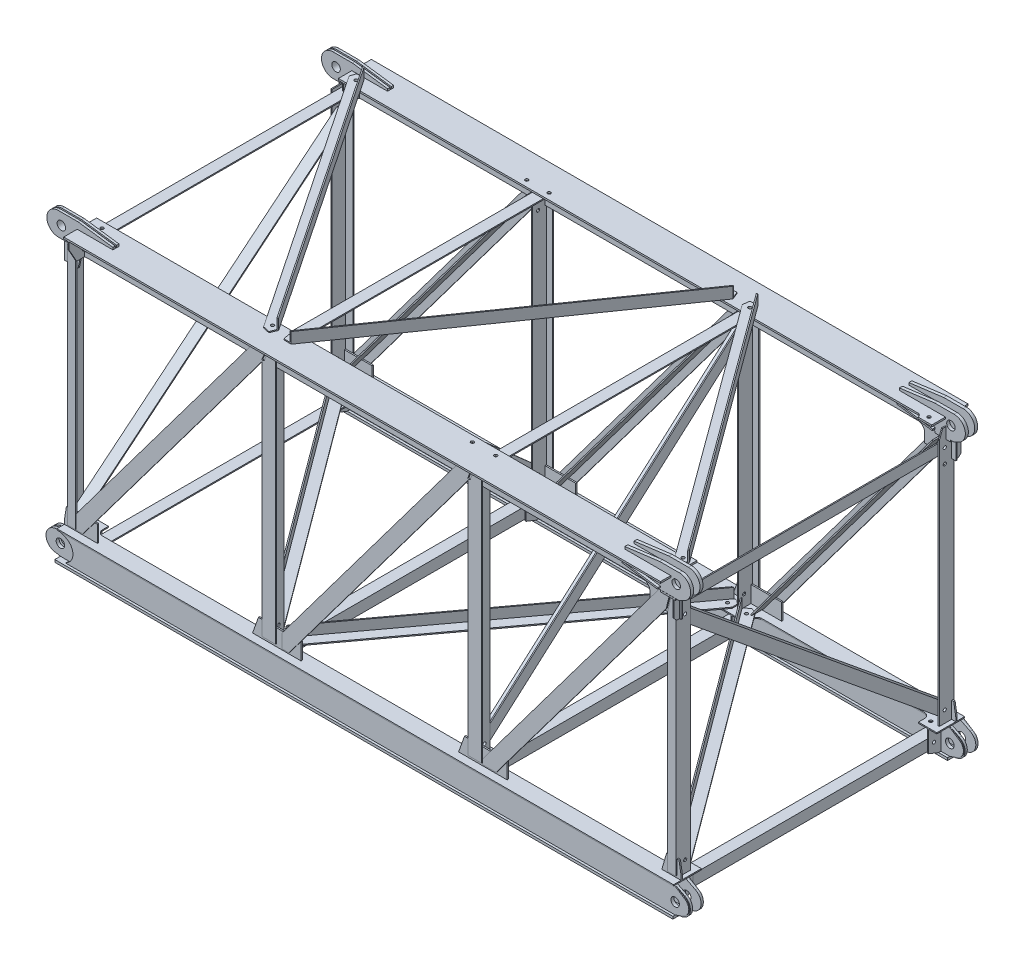
SolidWorks part; units mm, degrees
ref_plane "前视基准面" through (0, 0, 0) normal (0, 0, 1) x (1, 0, 0)
ref_plane "上视基准面" through (0, 0, 0) normal (0, 1, 0) x (1, 0, 0)
ref_plane "右视基准面" through (0, 0, 0) normal (1, 0, 0) x (0, 0, -1)
sketch "草图2" plane through (0, 0, 0) normal (0, 0, 1) x (1, 0, 0)
  line L0 (-1000, 2000) -> (49000, 2000) construction
  line L1 (-22, 1926) -> (5, 1926)
  line L2 (5, 1926) -> (5, 1776)
  line L3 (-22, 2074) -> (119, 2074)
  line L4 (5, 1776) -> (105, 1776)
  line L5 (117.1113, 1832.4829) -> (105, 1776)
  line L6 (166, 1872) -> (4218, 1872)
  line L7 (119, 2074) -> (375, 2040)
  line L8 (375, 2040) -> (375, 2022)
  line L9 (375, 2022) -> (4385, 2022)
  line L10 (4385, 2022) -> (4385, 1895)
  line L11 (4385, 1895) -> (4495, 1895)
  line L12 (4495, 1895) -> (4495, 1755)
  line L13 (4495, 1755) -> (4268, 1755)
  line L14 (4268, 1755) -> (4268, 1822)
  circle A0 centre (0, 2000) radius 31
  arc A1 (-22, 2074) -> (-22, 1926) centre (-22, 2000) ccw
  arc A2 (117.1113, 1832.4829) -> (166, 1872) centre (166, 1822) cw
  arc A3 (4268, 1822) -> (4218, 1872) centre (4218, 1822) ccw
  dimension "D1" = 62
  dimension "D4" = 74
  dimension "D10" = 50
  dimension "D19" = 50
  dimension "D2" = 2000
  dimension "D3" = 22
  dimension "D5" = 27
  dimension "D6" = 150
  dimension "D7" = 141
  dimension "D8" = 100
  dimension "D9" = 61
  dimension "D11" = 256
  dimension "D12" = 34
  dimension "D13" = 18
  dimension "D14" = 4010
  dimension "D15" = 127
  dimension "D16" = 110
  dimension "D17" = 140
  dimension "D18" = 227
  dimension "D20" = 117
extrude "凸台-拉伸1" add sketch "草图2" along normal blind 10
sketch "草图3" plane through (0, 2022, 0) normal (0, 1, 0) x (1, 0, 0)
  line L0 (-625, -5) -> (49375, -5) construction
  line L1 (375, -10) -> (375, 0) construction
  line L2 (115, 115) -> (115, 17)
  line L3 (115, 17) -> (375, 17)
  line L4 (375, 17) -> (375, -27)
  line L5 (375, -27) -> (115, -27)
  line L6 (115, -27) -> (115, -125)
  line L7 (115, -125) -> (4460, -125)
  line L8 (4460, -125) -> (4460, -50)
  line L9 (4460, -50) -> (4125, -50)
  line L10 (4125, -50) -> (4125, -28)
  line L11 (4125, -28) -> (4385, -28)
  line L12 (4385, -28) -> (4385, 18)
  line L13 (4385, 18) -> (4125, 18)
  line L14 (4125, 18) -> (4125, 40)
  line L15 (4125, 40) -> (4460, 40)
  line L16 (4460, 40) -> (4460, 140)
  line L17 (4335, 115) -> (115, 115)
  line L18 (4360, 140) -> (4460, 140)
  line L19 (4385, -10) -> (4385, 0) construction
  line L20 (-580.0707, 70) -> (49419.9293, 70) construction
  arc A0 (4335, 115) -> (4360, 140) centre (4335, 140) ccw
  circle A1 centre (199, 70) radius 11.5
  circle A2 centre (1440.6, 70) radius 11.5
  circle A3 centre (1604, 70) radius 11.5
  circle A4 centre (2896, 70) radius 11.5
  circle A5 centre (3066, 70) radius 11.5
  circle A6 centre (4400, 100) radius 11.5
  point P5 (375, -5)
  dimension "D8" = 25
  dimension "D12" = 23
  dimension "D18" = 23
  dimension "D1" = 44
  dimension "D2" = 98
  dimension "D3" = 260
  dimension "D4" = 4345
  dimension "D5" = 75
  dimension "D6" = 335
  dimension "D7" = 22
  dimension "D9" = 45
  dimension "D10" = 100
  dimension "D11" = 100
  dimension "D13" = 84
  dimension "D14" = 1241.6
  dimension "D15" = 163.4
  dimension "D16" = 170
  dimension "D17" = 1292
  dimension "D19" = 40
  dimension "D20" = 60
extrude "凸台-拉伸2" add sketch "草图3" along normal blind 12
sketch "草图4" plane through (0, 0, 0) normal (1, 0, 0) x (0, 0, -1)
  line L0 (-5, -1000) -> (-5, 49000) construction
  line L1 (-75, -82) -> (65, -82)
  line L2 (-75, -82) -> (-75, -100)
  line L3 (-75, -100) -> (-25, -100)
  line L4 (65, -82) -> (65, -100)
  line L5 (-5, 776) -> (-5, 50776) construction
  line L6 (-10, 1776) -> (0, 1776) construction
  line L7 (-25, -100) -> (-25, -90)
  line L8 (-25, -90) -> (15, -90)
  line L9 (15, -90) -> (15, -100)
  line L10 (15, -100) -> (65, -100)
  point P12 (-5, 1776)
  dimension "D1" = 140
  dimension "D2" = 18
  dimension "D3" = 82
  dimension "D4" = 10
  dimension "D5" = 50
  dimension "D6" = 50
extrude "凸台-拉伸3" add sketch "草图4" along normal blind 4500 separate body
sketch "草图5" plane through (0, 0, 0) normal (-1, 0, 0) x (0, 0, 1)
  line L0 (-65, -82) -> (75, -82) construction
  line L1 (-138, 110) -> (65, 110)
  line L2 (-138, 110) -> (-138, 102)
  line L3 (-138, 102) -> (65, 102)
  line L4 (65, 110) -> (65, 102)
  line L6 (5, 776) -> (5, 50776) construction
  line L7 (10, 1776) -> (0, 1776) construction
  point P14 (5, 1776)
  dimension "D1" = 184
  dimension "D2" = 60
  dimension "D3" = 203
  dimension "D4" = 8
extrude "凸台-拉伸4" add sketch "草图5" against normal blind 4495 separate body
sketch "草图6" plane through (0, 110, 0) normal (0, 1, 0) x (1, 0, 0)
  line L0 (4495, 138) -> (0, 138) construction
  line L1 (0, -65) -> (5, -65)
  line L2 (0, -65) -> (0, 138)
  line L3 (0, 138) -> (5, 138)
  line L4 (5, -65) -> (5, 138)
  line L5 (-62.0631, 88) -> (49937.9369, 88) construction
  line L6 (218, 55) -> (1360, 55)
  line L7 (4495, -65) -> (0, -65) construction
  line L8 (178, 138) -> (178, 95)
  line L9 (218, 95) -> (50218, 95) construction
  line L10 (1400, 95) -> (1400, 138)
  line L11 (1620, 138) -> (2880, 138)
  line L12 (1620, 138) -> (1620, 95)
  line L13 (1660, 55) -> (2840, 55)
  line L14 (2880, 95) -> (2880, 138)
  line L15 (3100, 138) -> (4361, 138)
  line L16 (3100, 138) -> (3100, 95)
  line L17 (3140, 55) -> (4321, 55)
  line L18 (4361, 95) -> (4361, 138)
  line L19 (178, 138) -> (1400, 138)
  circle A0 centre (98, 88) radius 11.5
  arc A1 (178, 95) -> (218, 55) centre (218, 95) ccw
  arc A2 (1360, 55) -> (1400, 95) centre (1360, 95) ccw
  circle A3 centre (1440, 88) radius 11.5
  circle A4 centre (1579, 88) radius 11.5
  arc A5 (1620, 95) -> (1660, 55) centre (1660, 95) ccw
  arc A6 (2840, 55) -> (2880, 95) centre (2840, 95) ccw
  arc A7 (3100, 95) -> (3140, 55) centre (3140, 95) ccw
  circle A8 centre (2921, 88) radius 11.5
  circle A9 centre (3059, 88) radius 11.5
  arc A10 (4321, 55) -> (4361, 95) centre (4321, 95) ccw
  circle A11 centre (4401, 88) radius 11.5
  dimension "D3" = 23
  dimension "D5" = 40
  dimension "D7" = 213
  dimension "D9" = 40
  dimension "D12" = 40
  dimension "D14" = 40
  dimension "D18" = 40
  dimension "D20" = 40
  dimension "D1" = 5
  dimension "D2" = 50
  dimension "D4" = 93
  dimension "D6" = 120
  dimension "D8" = 1142
  dimension "D10" = 1342
  dimension "D11" = 139
  dimension "D13" = 300
  dimension "D15" = 1180
  dimension "D16" = 1342
  dimension "D17" = 138
  dimension "D19" = 300
  dimension "D21" = 1181
  dimension "D22" = 1342
extrude "切除-拉伸1" cut sketch "草图6" against normal blind 8
sketch "草图7" plane through (0, 0, 0) normal (-1, 0, 0) x (0, 0, 1)
  line L0 (5, 926) -> (5, 50926) construction
  line L1 (10, 1926) -> (0, 1926) construction
  line L2 (65, 102) -> (-138, 102) construction
  line L3 (-48, 102) -> (-42, 102)
  line L4 (-48, 102) -> (-48, -82)
  line L5 (-48, -82) -> (-42, -82)
  line L6 (-42, 102) -> (-42, -82)
  line L7 (-65, -82) -> (75, -82) construction
  line L8 (75, -82) -> (75, -100) construction
  line L9 (52, 102) -> (58, 102)
  line L10 (52, 102) -> (52, -82)
  line L11 (52, -82) -> (58, -82)
  line L12 (58, 102) -> (58, -82)
  point P5 (5, 1926)
  point P17 (75, -91)
  dimension "D1" = 17
  dimension "D2" = 6
extrude "凸台-拉伸5" add sketch "草图7" against normal blind 4600
sketch "草图9" plane through (0, 0, 58) normal (0, 0, 1) x (1, 0, 0)
  line L0 (3424.3728, 0) -> (53424.3728, 0) construction
  line L1 (4500, -82) -> (0, -82) construction
  line L3 (4556.6629, -60.9212) -> (4500, -82)
  line L4 (4568.969, 54.7921) -> (4495, 102)
  line L5 (4600, 102) -> (4495, 102) construction
  line L6 (0, 102) -> (12, 102)
  line L7 (4495, 102) -> (5, 102) construction
  line L8 (12, 102) -> (12, 97)
  line L9 (0, 102) -> (0, -82)
  line L10 (0, -82) -> (66, -82)
  line L11 (4500, -82) -> (0, -82) construction
  line L12 (66, -82) -> (66, -77)
  line L13 (4495, 102) -> (4495, 110) construction
  line L14 (12, 97) -> (59.0619, 79.8775)
  line L15 (4500, 1374.2832) -> (4500, 51374.2832) construction
  line L16 (4495, 102) -> (4600, 102)
  line L17 (4600, 102) -> (4600, -82)
  line L18 (4600, -82) -> (4500, -82)
  circle A0 centre (4500, 0) radius 31
  arc A1 (4568.969, 54.7921) -> (4556.6629, -60.9212) centre (4534, 0) cw
  arc A2 (59.0619, 79.8775) -> (66, -77) centre (30, 0) cw
  circle A3 centre (0, 2000) radius 31 construction
  dimension "D2" = 62
  dimension "D3" = 65
  dimension "D5" = 85
  dimension "D6" = 4500
  dimension "D1" = 82
  dimension "D4" = 34
  dimension "D7" = 36
  dimension "D8" = 54
  dimension "D9" = 5
  dimension "D10" = 4434
extrude "切除-拉伸2" cut sketch "草图9" against normal through all
sketch "草图10" plane through (5, 0, 0) normal (-1, 0, 0) x (0, 0, 1)
  line L0 (5, -1090) -> (5, 48910) construction
  line L1 (25, -90) -> (-15, -90) construction
  line L2 (65, 110) -> (-138, 110) construction
  line L3 (0, 230) -> (10, 230)
  line L4 (0, 230) -> (0, 110)
  line L5 (0, 110) -> (10, 110)
  line L6 (10, 230) -> (10, 110)
  point P5 (5, -90)
  dimension "D1" = 120
  dimension "D2" = 10
extrude "凸台-拉伸6" add sketch "草图10" against normal blind 240 separate body
sketch "草图11" plane through (0, 0, 10) normal (0, 0, 1) x (1, 0, 0)
  line L0 (5, 230) -> (5, 140)
  line L1 (5, 110) -> (5, 230) construction
  line L2 (5, 140) -> (20, 230)
  line L3 (245, 230) -> (5, 230) construction
  line L4 (20, 230) -> (5, 230)
  line L5 (4495, 110) -> (5, 110) construction
  line L6 (245, 110) -> (245, 230) construction
  dimension "D1" = 30
  dimension "D2" = 225
extrude "切除-拉伸3" cut sketch "草图11" against normal through all
sketch "草图14" plane through (0, 0, 10) normal (0, 0, 1) x (1, 0, 0)
  line L0 (1500, -43.5219) -> (1500, 49956.4781) construction
  line L2 (1418, 230) -> (1728, 230)
  line L3 (1418, 230) -> (1375, 110)
  line L4 (1375, 110) -> (1728, 110)
  line L5 (1728, 230) -> (1728, 110)
  line L7 (4495, 110) -> (5, 110) construction
  line L8 (3000, 927.7111) -> (3000, 50927.7111) construction
  line L9 (4390, 230) -> (4355, 110)
  line L10 (4355, 110) -> (4495, 110)
  line L11 (2918, 230) -> (3228, 230)
  line L12 (2918, 230) -> (2875, 110)
  line L13 (2875, 110) -> (3228, 110)
  line L14 (3228, 230) -> (3228, 110)
  line L15 (4495, 110) -> (4495, 140)
  line L16 (4495, 140) -> (4480, 230)
  line L17 (4480, 230) -> (4390, 230)
  line L18 (4495, 102) -> (4495, 110) construction
  circle A0 centre (0, 2000) radius 31 construction
  dimension "D1" = 1500
  dimension "D2" = 125
  dimension "D3" = 1500
  dimension "D4" = 353
  dimension "D5" = 120
  dimension "D6" = 310
  dimension "D7" = 120
  dimension "D8" = 125
  dimension "D9" = 353
  dimension "D10" = 310
  dimension "D11" = 30
  dimension "D12" = 140
  dimension "D13" = 90
  dimension "D14" = 35
extrude "凸台-拉伸9" add sketch "草图14" against normal blind 10 separate body
sketch "草图12" plane through (0, 0, 10) normal (0, 0, 1) x (1, 0, 0)
  line L0 (3015, 2002) -> (2968, 1878)
  line L1 (35, 1896) -> (95, 1896)
  line L2 (35, 1896) -> (35, 125)
  line L3 (35, 125) -> (95, 125)
  line L4 (95, 1896) -> (95, 125)
  line L5 (5, 102) -> (5, 110) construction
  line L6 (245, 110) -> (5, 110) construction
  line L7 (1500, -109.2049) -> (1500, 49890.7951) construction
  line L8 (3000, -217.5113) -> (3000, 49782.4887) construction
  line L9 (1375, 110) -> (1728, 110) construction
  line L10 (1550, 2002) -> (1515, 2002)
  line L11 (1450, 1861) -> (1450, 130)
  line L12 (1450, 130) -> (1550, 130)
  line L13 (1550, 2002) -> (1550, 130)
  line L14 (3050, 2002) -> (3015, 2002)
  line L15 (2950, 1861) -> (2950, 130)
  line L16 (2950, 130) -> (3050, 130)
  line L17 (3050, 2002) -> (3050, 130)
  line L18 (2875, 110) -> (3228, 110) construction
  line L19 (1450, 1861) -> (1458, 1872)
  line L20 (2968, 1878) -> (2958, 1872)
  line L21 (1458, 1872) -> (1468, 1878)
  line L22 (1468, 1878) -> (1515, 2002)
  line L23 (2958, 1872) -> (2950, 1861)
  line L25 (4355, 110) -> (4495, 110) construction
  line L26 (4465, 1875) -> (4431, 1875)
  line L27 (4405, 1763) -> (4405, 125)
  line L28 (4405, 125) -> (4465, 125)
  line L29 (4465, 1875) -> (4465, 125)
  line L30 (4495, 110) -> (4495, 140) construction
  line L31 (4431, 1875) -> (4405, 1763)
  circle A0 centre (0, 2000) radius 31 construction
  point P4 (5, 106)
  point P39 (4425, 110)
  dimension "D9" = 1500
  dimension "D1" = 60
  dimension "D2" = 1771
  dimension "D3" = 30
  dimension "D4" = 15
  dimension "D5" = 100
  dimension "D6" = 100
  dimension "D7" = 20
  dimension "D8" = 20
  dimension "D10" = 1500
  dimension "D11" = 1731
  dimension "D12" = 1731
  dimension "D13" = 1872
  dimension "D14" = 1872
  dimension "D15" = 35
  dimension "D16" = 35
  dimension "D17" = 11
  dimension "D18" = 8
  dimension "D19" = 6
  dimension "D20" = 10
  dimension "D21" = 11
  dimension "D22" = 6
  dimension "D23" = 8
  dimension "D24" = 10
  dimension "D25" = 15
  dimension "D26" = 30
  dimension "D27" = 60
  dimension "D28" = 1750
  dimension "D29" = 1638
  dimension "D30" = 34
extrude "凸台-拉伸7" add sketch "草图12" along normal blind 8
sketch "草图13" plane through (0, 0, 10) normal (0, 0, -1) x (-1, 0, 0)
  line L0 (-35, 1776) -> (-35, 230) construction
  line L1 (-43, 1916) -> (-35, 1916)
  line L2 (-43, 1916) -> (-43, 110)
  line L3 (-43, 110) -> (-35, 110)
  line L4 (-35, 1916) -> (-35, 110)
  line L5 (-245, 110) -> (-5, 110) construction
  line L6 (-1500, -75.6357) -> (-1500, 49924.3643) construction
  line L7 (-3000, -284.4215) -> (-3000, 49715.5785) construction
  line L8 (-1660, 110) -> (-2840, 110) construction
  line L9 (-1550, 130) -> (-1550, 1872) construction
  line L10 (-1450, 1861) -> (-1450, 130) construction
  line L11 (-2950, 1861) -> (-2950, 130) construction
  line L12 (-3050, 130) -> (-3050, 1872) construction
  line L13 (-3004, 2022) -> (-2996, 2022)
  line L14 (-3004, 2022) -> (-3004, 110)
  line L15 (-3004, 110) -> (-2996, 110)
  line L16 (-2996, 2022) -> (-2996, 110)
  line L17 (-1504, 2022) -> (-1496, 2022)
  line L18 (-1504, 2022) -> (-1504, 110)
  line L19 (-1504, 110) -> (-1496, 110)
  line L20 (-1496, 2022) -> (-1496, 110)
  line L21 (-4385, 2022) -> (-375, 2022) construction
  line L23 (-4465, 125) -> (-4465, 1755) construction
  line L24 (-4465, 1977) -> (-4457, 1977)
  line L25 (-4465, 1977) -> (-4465, 110)
  line L26 (-4465, 110) -> (-4457, 110)
  line L27 (-4457, 1977) -> (-4457, 110)
  line L28 (-4355, 110) -> (-4495, 110) construction
  dimension "D1" = 8
  dimension "D2" = 1806
  dimension "D3" = 8
  dimension "D4" = 8
  dimension "D5" = 8
  dimension "D6" = 1867
extrude "凸台-拉伸8" add sketch "草图13" along normal blind 100
sketch "草图15" plane through (35, 0, 0) normal (-1, 0, 0) x (0, 0, 1)
  line L0 (-50, -217.3707) -> (-50, 49782.6293) construction
  line L1 (-90, 110) -> (-90, 1916) construction
  line L2 (-90, 110) -> (0, 110) construction
  circle A0 centre (-50, 195) radius 11.5
  circle A1 centre (-50, 1858) radius 11.5
  circle A2 centre (-50, 1745) radius 11.5
  dimension "D2" = 23
  dimension "D1" = 40
  dimension "D3" = 85
  dimension "D4" = 113
  dimension "D5" = 1550
extrude "切除-拉伸4" cut sketch "草图15" against normal blind 8
sketch "草图18" plane through (4465, 0, 0) normal (1, 0, 0) x (0, 0, -1)
  line L0 (-10, 1895) -> (0, 1895) construction
  line L1 (-10, 1977) -> (40, 1977)
  line L2 (-10, 1977) -> (-10, 1895)
  line L3 (-10, 1895) -> (40, 1895)
  line L4 (40, 1977) -> (40, 1895)
  line L5 (65, 1977) -> (90, 1911)
  line L6 (90, 1977) -> (-10, 1977) construction
  line L7 (90, 1977) -> (90, 110) construction
  line L8 (90, 1911) -> (90, 1977)
  line L9 (90, 1977) -> (65, 1977)
  line L10 (50, 650.9833) -> (50, 50650.9833) construction
  line L11 (90, 110) -> (-10, 110) construction
  circle A0 centre (50, 1848) radius 11.5
  circle A1 centre (50, 1745) radius 11.5
  circle A2 centre (50, 195) radius 11.5
  dimension "D5" = 23
  dimension "D7" = 23
  dimension "D8" = 23
  dimension "D1" = 50
  dimension "D2" = 25
  dimension "D3" = 66
  dimension "D4" = 40
  dimension "D6" = 85
  dimension "D9" = 103
  dimension "D10" = 63
extrude "切除-拉伸6" cut sketch "草图18" against normal blind 8
sketch "草图19" plane through (1496, 0, 0) normal (-1, 0, 0) x (0, 0, 1)
  line L0 (-50, -267.6002) -> (-50, 49732.3998) construction
  line L1 (-90, 110) -> (-90, 2022) construction
  line L2 (-90, 110) -> (10, 110) construction
  circle A0 centre (-50, 195) radius 11.5
  circle A1 centre (-50, 1962) radius 11.5
  circle A2 centre (-50, 1864) radius 11.5
  dimension "D2" = 23
  dimension "D3" = 23
  dimension "D4" = 23
  dimension "D5" = 85
  dimension "D1" = 40
  dimension "D6" = 1669
  dimension "D7" = 98
extrude "切除-拉伸7" cut sketch "草图19" against normal blind 1508
sketch "草图20" plane through (0, 0, 10) normal (0, 0, 1) x (1, 0, 0)
  line L0 (-1000, 2000) -> (49000, 2000) construction
  line L1 (0, 1000) -> (0, 51000) construction
  line L2 (-22, 2084) -> (120, 2084)
  line L3 (120, 2084) -> (375, 2050)
  line L4 (375, 2050) -> (375, 1945)
  line L5 (375, 1945) -> (120, 1916)
  line L6 (120, 1916) -> (-22, 1916)
  circle A0 centre (0, 2000) radius 31
  circle A1 centre (0, 2000) radius 31 construction
  arc A2 (-22, 2084) -> (-22, 1916) centre (-22, 2000) ccw
  dimension "D2" = 84
  dimension "D1" = 22
  dimension "D3" = 142
  dimension "D4" = 142
  dimension "D5" = 255
  dimension "D6" = 29
  dimension "D7" = 34
extrude "凸台-拉伸11" add sketch "草图20" along normal blind 17
pattern_linear "阵列(线性)3" count 2 spacing 27 along (0, 0, -1) of "凸台-拉伸11"
sketch "草图21" plane through (0, 0, 125) normal (0, 0, 1) x (1, 0, 0)
  line L0 (375, 2022) -> (115, 2022) construction
  line L1 (145, 2022) -> (153, 2022)
  line L2 (145, 2022) -> (145, 1872)
  line L3 (145, 1872) -> (153, 1872)
  line L4 (153, 2022) -> (153, 1872)
  dimension "D1" = 8
  dimension "D2" = 30
  dimension "D3" = 150
extrude "凸台-拉伸13" add sketch "草图21" against normal blind 98 separate body
sketch "草图22" plane through (145, 0, 0) normal (-1, 0, 0) x (0, 0, 1)
  line L0 (125, 1972) -> (68, 1872)
  line L1 (125, 2022) -> (125, 1872) construction
  line L2 (27, 1872) -> (125, 1872) construction
  line L3 (68, 1872) -> (125, 1872)
  line L4 (125, 1872) -> (125, 1972)
  dimension "D2" = 100
  dimension "D3" = 57
extrude "切除-拉伸8" cut sketch "草图22" against normal blind 8
sketch "草图23" plane through (145, 0, 0) normal (-1, 0, 0) x (0, 0, 1)
  line L0 (10, 1916) -> (10, 1776) construction
  line L1 (27, 1872) -> (10, 1872)
  line L2 (27, 1872) -> (27, 1916)
  line L3 (27, 1916) -> (10, 1916)
  line L4 (10, 1872) -> (10, 1916)
  line L6 (27, 1916) -> (10, 1916) construction
extrude "凸台-拉伸14" add sketch "草图23" against normal blind 8
sketch "草图24" plane through (145, 0, 0) normal (-1, 0, 0) x (0, 0, 1)
  line L0 (-115, 2022) -> (-115, 1972)
  line L1 (-115, 1972) -> (-58, 1872)
  line L2 (-58, 1872) -> (0, 1872)
  line L3 (0, 1872) -> (0, 1916)
  line L4 (0, 1916) -> (-17, 1916)
  line L5 (-17, 1916) -> (-17, 2022)
  line L6 (-17, 2022) -> (-115, 2022)
  line L7 (-115, 2022) -> (-17, 2022) construction
  line L8 (-115, 2034) -> (-115, 2022) construction
  line L9 (125, 2022) -> (125, 1972) construction
  line L10 (-17, 2034) -> (-17, 2022) construction
  line L11 (27, 1916) -> (10, 1916) construction
  line L12 (10, 1872) -> (68, 1872) construction
  line L13 (125, 1972) -> (68, 1872) construction
extrude "凸台-拉伸15" add sketch "草图24" against normal blind 8
ref_plane "基准面1" through (0, 0, -24) normal (0, 0, 1) x (1, 0, 0)
sketch "草图25" plane through (0, 0, -24) normal (0, 0, 1) x (1, 0, 0)
  line L0 (-1090.192, 0) -> (48909.808, 0) construction
  line L1 (4500, -82) -> (66, -82) construction
  line L2 (0, -82) -> (0, -100) construction
  line L3 (-43.932, -73.6946) -> (0, -82)
  line L4 (-44.9101, 73.503) -> (3.7772, 83.3792)
  line L5 (4495, 102) -> (5, 102) construction
  line L6 (19, 102) -> (275, 102)
  line L7 (275, 102) -> (275, -82)
  line L8 (275, -82) -> (0, -82)
  circle A0 centre (0, 0) radius 31
  arc A1 (-44.9101, 73.503) -> (-43.932, -73.6946) centre (-30, 0) ccw
  arc A2 (19, 102) -> (3.7772, 83.3792) centre (0, 102) cw
  dimension "D2" = 62
  dimension "D4" = 75
  dimension "D5" = 19
  dimension "D1" = 82
  dimension "D3" = 30
  dimension "D6" = 275
extrude "凸台-拉伸16" add sketch "草图25" along normal blind 22
pattern_linear "阵列(线性)4" count 2 spacing 36 along (0, 0, 1) of "凸台-拉伸16"
sketch "草图26" plane through (0, 0, -40) normal (0, 0, 1) x (1, 0, 0)
  line L0 (4500, 1491.3071) -> (4500, 51491.3071) construction
  line L1 (-1000, 2000) -> (49000, 2000) construction
  line L2 (4522, 2083) -> (4380, 2083)
  line L3 (4380, 2083) -> (4125, 2050)
  line L4 (4125, 2050) -> (4125, 1945)
  line L5 (4125, 1945) -> (4380, 1907)
  line L6 (4380, 1907) -> (4522.1862, 1907)
  line L8 (4522.1862, 1907) -> (4559.5899, 1926)
  circle A0 centre (0, 2000) radius 31 construction
  circle A1 centre (4500, 2000) radius 31
  arc A2 (4522, 2083) -> (4559.5899, 1926) centre (4522, 2000) cw
  dimension "D1" = 4500
  dimension "D2" = 62
  dimension "D4" = 83
  dimension "D3" = 22
  dimension "D5" = 255
  dimension "D6" = 142
  dimension "D7" = 33
  dimension "D8" = 105
  dimension "D9" = 38
  dimension "D10" = 19
extrude "凸台-拉伸17" add sketch "草图26" along normal blind 22
pattern_linear "阵列(线性)5" count 2 spacing 68 along (0, 0, 1) of "凸台-拉伸17"
sketch "草图27" plane through (0, 0, -40) normal (0, 0, 1) x (1, 0, 0)
  line L0 (4380, 1907) -> (4522.1862, 1907) construction
  line L1 (4385, 1895) -> (4495, 1895)
  line L2 (4385, 1895) -> (4385, 1907)
  line L3 (4385, 1907) -> (4495, 1907)
  line L4 (4495, 1895) -> (4495, 1907)
  line L5 (4495, 1755) -> (4495, 1895) construction
extrude "凸台-拉伸18" add sketch "草图27" along normal blind 91
sketch "草图28" plane through (0, 0, 10) normal (0, 0, 1) x (1, 0, 0)
  line L0 (4495, 1895) -> (4385, 1895) construction
  line L1 (4476, 1895) -> (4484, 1895)
  line L2 (4476, 1895) -> (4476, 1755)
  line L3 (4476, 1755) -> (4484, 1755)
  line L4 (4484, 1895) -> (4484, 1755)
  line L6 (4480, 837.8476) -> (4480, 50837.8476) construction
  line L7 (4465, 1755) -> (4465, 1875) construction
  line L8 (4495, 1755) -> (4495, 1895) construction
  dimension "D1" = 140
  dimension "D2" = 8
extrude "凸台-拉伸19" add sketch "草图28" along normal blind 40
sketch "草图29" plane through (4484, 0, 0) normal (1, 0, 0) x (0, 0, -1)
  line L0 (-50, 1775) -> (-30, 1755)
  line L1 (-50, 1755) -> (-50, 1895) construction
  line L3 (-30, 1755) -> (-50, 1755)
  line L4 (-50, 1755) -> (-50, 1775)
  line L5 (-51, 1895) -> (-10, 1895) construction
  line L8 (-10, 1755) -> (-10, 1895) construction
  dimension "D1" = 120
  dimension "D2" = 20
extrude "切除-拉伸9" cut sketch "草图29" against normal blind 8
sketch "草图30" plane through (0, 0, 50) normal (0, 0, 1) x (1, 0, 0)
  line L0 (4125, 1945) -> (4380, 1907) construction
  line L1 (4126.7687, 1969.0014) -> (4385, 1930.5199)
  line L2 (4126.7687, 1969.0014) -> (4125, 1957.1325)
  line L3 (4125, 1957.1325) -> (4383.2313, 1918.651)
  line L4 (4385, 1930.5199) -> (4383.2313, 1918.651)
  line L5 (4385, 1895) -> (4385, 1907) construction
  line L6 (4125, 2022) -> (4125, 1945) construction
  dimension "D1" = 12
  dimension "D2" = 12
extrude "凸台-拉伸20" add sketch "草图30" along normal blind 19
pattern_linear "阵列(线性)6" count 2 spacing 109 along (0, 0, -1) of "凸台-拉伸20"
sketch "草图31" plane through (0, 0, -42) normal (0, 0, 1) x (1, 0, 0)
  line L0 (4500, 0) -> (54500, 0) construction
  line L1 (4495, 102) -> (4290, 102)
  line L2 (4290, 102) -> (4290, -82)
  line L3 (4290, -82) -> (4500, -82)
  line L4 (4500, -82) -> (4543.932, -73.6946)
  line L5 (4495, 102) -> (4564.0432, 66.8286)
  line L6 (4495, 102) -> (5, 102) construction
  line L7 (4500, -82) -> (0, -82) construction
  circle A0 centre (4500, 0) radius 31
  circle A1 centre (4500, 0) radius 31 construction
  arc A2 (4564.0432, 66.8286) -> (4543.932, -73.6946) centre (4530, 0) cw
  dimension "D2" = 75
  dimension "D1" = 30
  dimension "D3" = 210
  dimension "D4" = 205
extrude "凸台-拉伸21" add sketch "草图31" along normal blind 16
pattern_linear "阵列(线性)7" count 2 spacing 78 along (0, 0, 1) of "凸台-拉伸21"
sketch "草图32" plane through (0, 0, -48) normal (0, 0, -1) x (-1, 0, 0)
  line L0 (-4431, -423.4319) -> (-4431, 49576.5681) construction
  line L1 (-3000, -505.8773) -> (-3000, 49494.1227) construction
  line L2 (-1500, -83.8374) -> (-1500, 49916.1626) construction
  line L3 (-98, -959.1022) -> (-98, 49040.8978) construction
  line L4 (-3004, 2022) -> (-3004, 110) construction
  line L5 (-2996, 130) -> (-2996, 1872) construction
  line L6 (-1496, 130) -> (-1496, 1872) construction
  line L7 (-1504, 1872) -> (-1504, 130) construction
  line L8 (-4495, 102) -> (-12, 102) construction
  line L9 (-3004, 102) -> (-2996, 102)
  line L10 (-3004, 102) -> (-3004, -82)
  line L11 (-3004, -82) -> (-2996, -82)
  line L12 (-2996, 102) -> (-2996, -82)
  line L13 (-4500, -82) -> (0, -82) construction
  line L14 (-1620, 102) -> (-1400, 102) construction
  line L15 (-1504, 102) -> (-1496, 102)
  line L16 (-1504, 102) -> (-1504, -82)
  line L17 (-1504, -82) -> (-1496, -82)
  line L18 (-1496, 102) -> (-1496, -82)
  line L20 (-66, 102) -> (-74, 102)
  line L21 (-66, 102) -> (-66, -82)
  line L22 (-66, -82) -> (-74, -82)
  line L23 (-4495, 102) -> (-4361, 102) construction
  line L24 (-4435, 102) -> (-4427, 102)
  line L25 (-4435, 102) -> (-4435, -82)
  line L26 (-4435, -82) -> (-4427, -82)
  line L27 (-4427, 102) -> (-4427, -82)
  line L28 (-4500, -82) -> (-66, -82) construction
  line L29 (-178, 102) -> (-5, 102) construction
  line L30 (-122, 102) -> (-130, 102)
  line L31 (-122, 102) -> (-122, -82)
  line L32 (-122, -82) -> (-130, -82)
  line L33 (-130, 102) -> (-130, -82)
  line L34 (-4457, 110) -> (-4457, 1911) construction
  line L35 (-4405, 1755) -> (-4405, 125) construction
  line L38 (-74, 102) -> (-74, -82)
  line L39 (-66, -77) -> (-66, -82) construction
  line L40 (-5, 102) -> (-5, 110) construction
  dimension "D1" = 8
  dimension "D2" = 8
  dimension "D3" = 8
  dimension "D4" = 8
  dimension "D5" = 8
  dimension "D6" = 93
extrude "凸台-拉伸22" add sketch "草图32" along normal blind 90
sketch "草图33" plane through (122, 0, 0) normal (-1, 0, 0) x (0, 0, 1)
  line L0 (-138, -82) -> (-65, -82)
  line L1 (-138, -82) -> (-65, -82) construction
  line L2 (-65, -82) -> (-138, -53)
  line L3 (-138, -82) -> (-138, 102) construction
  line L4 (-138, -53) -> (-138, -82)
  line L5 (-138, 102) -> (-48, 102) construction
  line L7 (-65, -100) -> (-65, -82) construction
  circle A0 centre (-98, 0) radius 11.5
  dimension "D1" = 23
  dimension "D2" = 40
  dimension "D3" = 102
  dimension "D4" = 29
extrude "切除-拉伸10" cut sketch "草图33" against normal through all
sketch "草图62" plane through (74, 0, 0) normal (1, 0, 0) x (0, 0, -1)
  line L0 (138, -82) -> (138, -53)
  line L1 (138, 102) -> (138, -82) construction
  line L2 (138, -53) -> (65, -82)
  line L3 (138, -82) -> (65, -82) construction
  line L4 (65, -82) -> (138, -82)
  line L5 (65, -82) -> (138, -53) construction
extrude "切除-拉伸13" cut sketch "草图62" against normal blind 8
sketch "草图57" plane through (0, 0, 10) normal (0, 0, 1) x (1, 0, 0)
  line L0 (0, 2000) -> (50000, 2000) construction
  line L1 (0, 0) -> (50000, 0) construction
  line L2 (0, 2000) -> (0, -48000) construction
  line L3 (4500, 2000) -> (4500, -48000) construction
  line L4 (1500, -870) -> (1500, 49130) construction
  line L5 (1450, 130) -> (1550, 130) construction
  line L6 (3156.25, 125) -> (3057.5, 125)
  line L7 (3057.5, 125) -> (3057.5, 160)
  line L8 (3000, -870) -> (3000, 49130) construction
  line L9 (2950, 130) -> (3050, 130) construction
  line L10 (1500, 2000) -> (0, 0) construction
  line L11 (1500, 0) -> (3000, 2000) construction
  line L12 (3000, 0) -> (4500, 2000) construction
  line L13 (1457.9999, 1872) -> (147.7499, 125)
  line L14 (1457.9999, 1872) -> (1450.7999, 1877.4)
  line L15 (1450.7999, 1877.4) -> (1505.9999, 1996)
  line L16 (1505.9999, 1996) -> (1433.1999, 2005.6)
  line L18 (1433.1999, 2005.6) -> (96.4999, 223.3333)
  line L19 (245, 110) -> (5, 110) construction
  line L21 (166, 1872) -> (1458, 1872) construction
  line L22 (96.4999, 223.3333) -> (96.4999, 125)
  line L23 (2875, 110) -> (3228, 110) construction
  line L24 (96.4999, 125) -> (147.7499, 125)
  line L25 (2933.7999, 2006.4) -> (1596.5499, 223.4)
  line L26 (2957.9999, 1872) -> (1647.7499, 125)
  line L27 (2957.9999, 1872) -> (2950.7999, 1877.4)
  line L28 (1550, 1872) -> (2958, 1872) construction
  line L29 (2950.7999, 1877.4) -> (2993.7999, 2006.4)
  line L30 (2993.7999, 2006.4) -> (2933.7999, 2006.4)
  line L31 (1375, 110) -> (1728, 110) construction
  line L32 (1647.7499, 125) -> (1596.3499, 124.8)
  line L33 (1596.3499, 124.8) -> (1596.5499, 223.4)
  line L34 (1549.1499, 160.2) -> (1629.1499, 100.2) construction
  line L35 (4394.35, 1775.8) -> (4418.75, 1875)
  line L36 (4418.75, 1875) -> (4343.75, 1875)
  line L37 (4394.35, 1775.8) -> (3156.25, 125)
  line L38 (4465, 1875) -> (4431, 1875) construction
  line L39 (4418.75, 1875) -> (44418.75, -28125) construction
  line L40 (3057.5, 160) -> (4343.75, 1875)
  point P17 (1500, 130)
  point P22 (3000, 130)
  dimension "D1" = 9
  dimension "D2" = 100
  dimension "D3" = 128
  dimension "D4" = 36
  dimension "D5" = 92
  dimension "D6" = 0.0001
  dimension "D7" = 15
  dimension "D8" = 59
  dimension "D9" = 0.0001
  dimension "D10" = 100
  dimension "D11" = 9
  dimension "D12" = 93
  dimension "D13" = 48
  dimension "D14" = 129
  dimension "D15" = 15
  dimension "D16" = 31
  dimension "D17" = 79
  dimension "D18" = 59
  dimension "D19" = 15
  dimension "D20" = 79
  dimension "D21" = 60
  dimension "D22" = 100
  dimension "D23" = 94
extrude "凸台-拉伸43" add sketch "草图57" along normal blind 8
sketch "草图58" plane through (0, 0, 10) normal (0, 0, 1) x (1, 0, 0)
  line L0 (1639.4445, 2197.2595) -> (-28360.5555, -37802.7405) construction
  line L1 (1433.1999, 2005.6) -> (96.4999, 223.3333) construction
  line L2 (147.7499, 125) -> (1457.9999, 1872) construction
  line L3 (1485.4999, 1998.6667) -> (96.4999, 146.6667)
  line L5 (96.4999, 146.6667) -> (102.8999, 141.8667)
  line L6 (102.8999, 141.8667) -> (1491.8999, 1993.8667)
  line L7 (1491.8999, 1993.8667) -> (1485.4999, 1998.6667)
  line L8 (96.4999, 223.3333) -> (96.4999, 125) construction
  line L10 (3245.8445, 2339.1261) -> (-26754.1555, -37660.8739) construction
  line L11 (1726.4999, 230) -> (2957.9999, 1872) construction
  line L12 (2832.9999, 1872) -> (1601.4999, 230) construction
  line L13 (2985.394, 1998.5254) -> (1596.394, 146.5254)
  line L14 (1596.394, 146.5254) -> (1602.794, 141.7254)
  line L15 (1602.794, 141.7254) -> (2991.794, 1993.7254)
  line L16 (2991.794, 1993.7254) -> (2985.394, 1998.5254)
  line L18 (1596.5499, 223.4) -> (1596.3499, 124.8) construction
  line L19 (4622.3378, 2163.1171) -> (-25377.6622, -37836.8829) construction
  line L20 (3228, 220.6667) -> (4378.75, 1755) construction
  line L21 (4268, 1774) -> (3110, 230) construction
  line L22 (4419.35, 1885.8) -> (3098.75, 125)
  line L23 (3098.75, 125) -> (3092.35, 129.8)
  line L24 (3092.35, 129.8) -> (4412.95, 1890.6)
  line L25 (4412.95, 1890.6) -> (4419.35, 1885.8)
  line L27 (3057.5, 125) -> (3156.25, 125) construction
  dimension "D1" = 8
  dimension "D2" = 2315
  dimension "D3" = 8
  dimension "D4" = 2315
  dimension "D5" = 8
  dimension "D6" = 2201
extrude "凸台-拉伸44" add sketch "草图58" against normal blind 100
sketch "草图59" plane through (-8.6401, 6.48, 0) normal (-0.8, 0.6, 0) x (0, 0, 1)
  line L0 (-90, 2490.2333) -> (-90, 2405.2333)
  line L1 (-90, 2490.2333) -> (-90, 175.2333) construction
  line L2 (-90, 2405.2333) -> (-30, 2435.2333)
  line L3 (-90, 2490.2333) -> (-30, 2490.2333)
  line L4 (-90, 2490.2333) -> (0, 2490.2333) construction
  line L5 (-30, 2490.2333) -> (-30, 2435.2333)
  dimension "D1" = 60
  dimension "D2" = 85
  dimension "D3" = 55
extrude "切除-拉伸11" cut sketch "草图59" against normal blind 8
sketch "草图61" plane through (951.3599, -713.52, 0) normal (-0.8, 0.6, 0) x (0, 0, 1)
  line L0 (-90, 3390.0567) -> (-90, 3305.0567)
  line L1 (-90, 3390.0567) -> (-90, 1075.0567) construction
  line L2 (-90, 3305.0567) -> (-30, 3335.0567)
  line L3 (-30, 3335.0567) -> (-30, 3390.0567)
  line L4 (-30, 3390.0567) -> (-90, 3390.0567)
  line L5 (-90, 3390.0567) -> (0, 3390.0567) construction
  dimension "D1" = 85
  dimension "D2" = 55
  dimension "D3" = 60
extrude "切除-拉伸12" cut sketch "草图61" against normal blind 8
ref_plane "基准面2" through (0, 0, -995) normal (0, 0, 1) x (1, 0, 0)
mirror "镜向1" about plane through (0, 0, -995) normal (0, 0, 1) of bodies 182 146
sketch "草图34" plane through (4427, 0, 0) normal (-1, 0, 0) x (0, 0, 1)
  line L0 (-1861.0606, 0) -> (48138.9394, 0) construction
  line L1 (-98, 0) -> (-50098, 0) construction
  line L3 (-1932, 37) -> (-58, 37)
  line L4 (-1932, 37) -> (-1932, -43)
  line L5 (-1932, -43) -> (-58, -43)
  line L6 (-58, 37) -> (-58, -43)
  circle A0 centre (-98, 0) radius 11.5
  circle A1 centre (-98, 0) radius 11.5 construction
  circle A2 centre (-1892, 0) radius 11.5
  circle A3 centre (-1892, 0) radius 11.5 construction
  dimension "D4" = 40
  dimension "D1" = 37
  dimension "D2" = 80
  dimension "D3" = 40
extrude "凸台-拉伸23" add sketch "草图34" along normal blind 8
sketch "草图35" plane through (4419, 0, 0) normal (-1, 0, 0) x (0, 0, 1)
  line L0 (-58, 37) -> (-1932, 37) construction
  line L1 (-58, 37) -> (-1932, 37)
  line L2 (-58, 37) -> (-58, 29)
  line L3 (-58, 29) -> (-1932, 29)
  line L4 (-1932, 37) -> (-1932, 29)
  line L5 (-1932, 37) -> (-1932, -43) construction
  dimension "D1" = 8
extrude "凸台-拉伸24" add sketch "草图35" along normal blind 72
pattern_linear "阵列(线性)8" count 2 spacing 1431 along (-1, 0, 0) of "凸台-拉伸23", "凸台-拉伸24"
pattern_linear "阵列(线性)12" count 2 spacing 2931 along (-1, 0, 0) of "凸台-拉伸23", "凸台-拉伸24"
ref_plane "基准面3" through (2278.5, 0, 0) normal (-1, 0, 0) x (0, 0, 1)
mirror "镜向2" about plane through (2278.5, 0, 0) normal (-1, 0, 0) of "凸台-拉伸23", "凸台-拉伸24"
sketch "草图36" plane through (0, 110, 0) normal (0, 1, 0) x (1, 0, 0)
  line L0 (98, 1902) -> (1440, 88) construction
  line L1 (1579, 88) -> (2921, 1902) construction
  line L2 (3059, 1902) -> (4401, 88) construction
  line L3 (52.197, 1901.7004) -> (51.7663, 1927.5038)
  line L4 (51.7663, 1927.5038) -> (85.5308, 1952.4829)
  line L5 (85.5308, 1952.4829) -> (121.8632, 1942.0443)
  line L6 (121.8632, 1942.0443) -> (1485.2738, 99.1033)
  line L7 (1485.2738, 99.1033) -> (1484.6259, 61.3067)
  line L8 (1484.6259, 61.3067) -> (1450.8613, 36.3276)
  line L9 (1450.8613, 36.3276) -> (1426.313, 44.2888)
  line L10 (1426.313, 44.2888) -> (52.197, 1901.7004)
  line L11 (85.5308, 1952.4829) -> (29822.5264, -38243.4261) construction
  line L12 (51.7663, 1927.5038) -> (29788.7618, -38268.4052) construction
  line L13 (2966.2738, 1890.8967) -> (2965.6259, 1928.6933)
  line L14 (2907.313, 1945.7112) -> (1533.197, 88.2996)
  line L15 (1533.197, 88.2996) -> (1532.7663, 62.4962)
  line L16 (1532.7663, 62.4962) -> (1566.5308, 37.5171)
  line L17 (1566.5308, 37.5171) -> (1602.8632, 47.9557)
  line L18 (1602.8632, 47.9557) -> (2966.2738, 1890.8967)
  line L19 (2965.6259, 1928.6933) -> (2931.8613, 1953.6724)
  line L20 (2929.3076, 1950.2205) -> (-26807.6879, -38245.6885) construction
  line L21 (2931.8613, 1953.6724) -> (2907.313, 1945.7112)
  line L22 (2965.6259, 1928.6933) -> (-26771.3696, -38267.2157) construction
  line L23 (3013.197, 1901.7004) -> (4387.313, 44.2888)
  line L24 (3082.8632, 1942.0443) -> (4446.2738, 99.1033)
  line L25 (3013.197, 1901.7004) -> (3012.7663, 1927.5038)
  line L26 (3012.7663, 1927.5038) -> (3046.5308, 1952.4829)
  line L27 (3046.5308, 1952.4829) -> (3082.8632, 1942.0443)
  line L28 (3012.7425, 1927.536) -> (32749.6782, -38268.2921) construction
  line L29 (3046.5572, 1952.4473) -> (32783.4928, -38243.3808) construction
  line L30 (4387.313, 44.2888) -> (4411.8613, 36.3276)
  line L31 (4411.8613, 36.3276) -> (4445.6259, 61.3067)
  line L32 (4445.6259, 61.3067) -> (4446.2738, 99.1033)
  circle A0 centre (3059, 1902) radius 11.5 construction
  circle A1 centre (4401, 88) radius 11.5 construction
  circle A2 centre (98, 1902) radius 11.5
  circle A3 centre (98, 1902) radius 11.5 construction
  circle A4 centre (1579, 88) radius 11.5
  circle A5 centre (1579, 88) radius 11.5 construction
  circle A6 centre (1440, 88) radius 11.5
  circle A7 centre (1440, 88) radius 11.5 construction
  circle A8 centre (3059, 1902) radius 11.5
  circle A9 centre (2921, 1902) radius 11.5
  circle A10 centre (2921, 1902) radius 11.5 construction
  circle A11 centre (4401, 88) radius 11.5
  dimension "D1" = 80
  dimension "D3" = 48
  dimension "D4" = 30
  dimension "D5" = 21
  dimension "D6" = 23
  dimension "D7" = 15
  dimension "D8" = 48
  dimension "D9" = 80
  dimension "D10" = 37
  dimension "D11" = 48
  dimension "D12" = 48
  dimension "D13" = 30
  dimension "D14" = 21
  dimension "D15" = 23
  dimension "D16" = 15
  dimension "D17" = 48
  dimension "D18" = 80
  dimension "D19" = 43
  dimension "D20" = 23
  dimension "D21" = 30
  dimension "D22" = 21
  dimension "D23" = 15
  dimension "D24" = 48
  dimension "D25" = 37
extrude "凸台-拉伸25" add sketch "草图36" along normal blind 8
sketch "草图37" plane through (0, 118, 0) normal (0, 1, 0) x (1, 0, 0)
  line L0 (4400.4054, 40.0429) -> (4387.313, 44.2888)
  line L2 (4387.313, 44.2888) -> (3013.197, 1901.7004)
  line L4 (3013.197, 1901.7004) -> (3012.9673, 1915.4622)
  line L5 (3012.9673, 1915.4622) -> (4400.4054, 40.0429)
  line L6 (1532.9673, 74.5378) -> (1533.197, 88.2996)
  line L8 (1533.197, 88.2996) -> (2907.313, 1945.7112)
  line L9 (2907.313, 1945.7112) -> (1533.197, 88.2996) construction
  line L10 (2907.313, 1945.7112) -> (2920.4054, 1949.9571)
  line L11 (2920.4054, 1949.9571) -> (1532.9673, 74.5378)
  line L12 (1439.4054, 40.0429) -> (1426.313, 44.2888)
  line L13 (2931.8613, 1953.6724) -> (2907.313, 1945.7112) construction
  line L14 (1426.313, 44.2888) -> (52.197, 1901.7004)
  line L15 (1533.197, 88.2996) -> (1532.7663, 62.4962) construction
  line L16 (52.197, 1901.7004) -> (51.9673, 1915.4622)
  line L17 (51.9673, 1915.4622) -> (1439.4054, 40.0429)
  line L18 (52.197, 1901.7004) -> (1426.313, 44.2888) construction
  line L19 (51.7663, 1927.5038) -> (52.197, 1901.7004) construction
  line L20 (1426.313, 44.2888) -> (1450.8613, 36.3276) construction
  line L22 (3013.197, 1901.7004) -> (4387.313, 44.2888) construction
  line L23 (3012.7663, 1927.5038) -> (3013.197, 1901.7004) construction
  line L24 (4387.313, 44.2888) -> (4411.8613, 36.3276) construction
  dimension "D1" = 8
  dimension "D2" = 8
  dimension "D3" = 8
extrude "凸台-拉伸26" add sketch "草图37" along normal blind 72
sketch "草图40" plane through (43, 0, 0) normal (1, 0, 0) x (0, 0, -1)
  line L0 (50, 195) -> (1940, 1745) construction
  line L1 (7.9798, 208.3903) -> (8.3071, 168.5671)
  line L2 (7.9798, 208.3903) -> (1935.0947, 1788.8285)
  line L3 (8.3071, 168.5671) -> (54.8439, 143.3615)
  line L4 (1989.6911, 1730.1409) -> (54.8439, 143.3615)
  line L5 (4.559, 173.1373) -> (31710.9846, -38488.2462) construction
  line L7 (1935.0947, 1788.8285) -> (1974.0834, 1780.7117)
  line L8 (1974.0834, 1780.7117) -> (1989.6911, 1730.1409)
  line L9 (1969.0392, 1786.8623) -> (-29737.3865, 40448.2459) construction
  circle A1 centre (50, 195) radius 11.5
  circle A3 centre (1940, 1745) radius 11.5
  circle A6 centre (50, 195) radius 11.5 construction
  circle A7 centre (1940, 1745) radius 11.5 construction
  dimension "D1" = 80
  dimension "D2" = 37
  dimension "D3" = 49
  dimension "D4" = 25
  dimension "D5" = 20
  dimension "D6" = 49
  dimension "D7" = 49
  dimension "D8" = 25
  dimension "D9" = 20
  dimension "D10" = 49
extrude "凸台-拉伸27" add sketch "草图40" along normal blind 8
sketch "草图41" plane through (51, 0, 0) normal (1, 0, 0) x (0, 0, -1)
  line L0 (7.9798, 208.3903) -> (8.0642, 198.1134)
  line L1 (7.9798, 208.3903) -> (8.3071, 168.5671) construction
  line L2 (8.0642, 198.1134) -> (1945.1563, 1786.7338)
  line L3 (1945.1563, 1786.7338) -> (1935.0947, 1788.8285)
  line L4 (1935.0947, 1788.8285) -> (7.9798, 208.3903) construction
  line L5 (1935.0947, 1788.8285) -> (7.9798, 208.3903)
  line L6 (1974.0834, 1780.7117) -> (1935.0947, 1788.8285) construction
  dimension "D1" = 8
extrude "凸台-拉伸28" add sketch "草图41" along normal blind 72
sketch "草图42" plane through (1496, 0, 0) normal (-1, 0, 0) x (0, 0, 1)
  line L0 (-1940, 195) -> (-50, 1864) construction
  line L1 (-1972.7575, 158.0683) -> (-1990.2003, 208.0358)
  line L2 (-1990.2003, 208.0358) -> (-56.7251, 1915.4274)
  line L3 (-56.7251, 1915.4274) -> (-9.2995, 1891.9368)
  line L4 (-9.2995, 1891.9368) -> (-7.5191, 1852.152)
  line L5 (-7.5191, 1852.152) -> (-1933.4986, 151.3797)
  line L6 (-1933.4986, 151.3797) -> (-1972.7575, 158.0683)
  line L7 (-6.8299, 1889.1402) -> (-33102.9937, 39367.72) construction
  line L8 (-1972.8481, 158.171) -> (-35069.0119, 37636.7507) construction
  circle A0 centre (-1940, 195) radius 11.5
  circle A2 centre (-50, 1864) radius 11.5
  circle A4 centre (-1940, 195) radius 11.5 construction
  circle A5 centre (-50, 1864) radius 11.5 construction
  dimension "D1" = 80
  dimension "D2" = 43
  dimension "D3" = 49
  dimension "D4" = 20
  dimension "D5" = 25
  dimension "D6" = 31
  dimension "D7" = 49
  dimension "D8" = 20
  dimension "D9" = 25
  dimension "D10" = 31
extrude "凸台-拉伸29" add sketch "草图42" along normal blind 8
sketch "草图43" plane through (1488, 0, 0) normal (-1, 0, 0) x (0, 0, 1)
  line L0 (-1943.6299, 153.1058) -> (-1933.4986, 151.3797)
  line L2 (-1933.4986, 151.3797) -> (-7.5191, 1852.152)
  line L3 (-7.5191, 1852.152) -> (-7.9786, 1862.4191)
  line L5 (-7.9786, 1862.4191) -> (-1943.6299, 153.1058)
  line L7 (-1972.7575, 158.0683) -> (-1933.4986, 151.3797) construction
  line L8 (-1933.4986, 151.3797) -> (-7.5191, 1852.152) construction
  line L9 (-7.5191, 1852.152) -> (-9.2995, 1891.9368) construction
  dimension "D1" = 8
extrude "凸台-拉伸30" add sketch "草图43" along normal blind 72
sketch "草图44" plane through (2996, 0, 0) normal (-1, 0, 0) x (0, 0, 1)
  line L0 (-1940, 1864) -> (-50, 195) construction
  line L1 (-52.7536, 148.0701) -> (-17.2425, 158.0683)
  line L2 (-17.2425, 158.0683) -> (0.2003, 208.0358)
  line L3 (0.2003, 208.0358) -> (-1933.2749, 1915.4274)
  line L4 (-1933.2749, 1915.4274) -> (-1980.7005, 1891.9368)
  line L5 (-1980.7005, 1891.9368) -> (-1982.4809, 1852.152)
  line L6 (-1982.4809, 1852.152) -> (-52.7536, 148.0701)
  line L7 (-25.2945, 148.9502) -> (33070.8693, 37627.5299) construction
  line L8 (-1973.6381, 1899.9345) -> (31122.5257, 39378.5142) construction
  circle A0 centre (-1940, 1864) radius 11.5
  circle A1 centre (-1940, 1864) radius 11.5 construction
  circle A2 centre (-50, 195) radius 11.5
  circle A3 centre (-50, 195) radius 11.5 construction
  dimension "D1" = 43
  dimension "D2" = 80
  dimension "D3" = 49
  dimension "D4" = 20
  dimension "D5" = 20
  dimension "D6" = 31
  dimension "D7" = 49
  dimension "D8" = 31
  dimension "D9" = 20
  dimension "D10" = 25
extrude "凸台-拉伸31" add sketch "草图44" along normal blind 8
sketch "草图45" plane through (2988, 0, 0) normal (-1, 0, 0) x (0, 0, 1)
  line L0 (-1982.0214, 1862.4191) -> (-1982.4809, 1852.152)
  line L2 (-1982.4809, 1852.152) -> (-52.7536, 148.0701)
  line L3 (-52.7536, 148.0701) -> (-43.5894, 150.6503)
  line L5 (-43.5894, 150.6503) -> (-1982.0214, 1862.4191)
  line L7 (-1982.4809, 1852.152) -> (-52.7536, 148.0701) construction
  line L8 (-52.7536, 148.0701) -> (-17.2425, 158.0683) construction
  line L9 (-1980.7005, 1891.9368) -> (-1982.4809, 1852.152) construction
  dimension "D1" = 8
extrude "凸台-拉伸32" add sketch "草图45" along normal blind 72
sketch "草图46" plane through (4457, 0, 0) normal (-1, 0, 0) x (0, 0, 1)
  line L0 (-1940, 195) -> (-50, 1745) construction
  line L1 (-54.9053, 1788.8285) -> (-15.9166, 1780.7117)
  line L2 (-15.9166, 1780.7117) -> (-0.3089, 1730.1409)
  line L3 (-0.3089, 1730.1409) -> (-1935.1561, 143.3615)
  line L4 (-1935.1561, 143.3615) -> (-1981.6929, 168.5671)
  line L5 (-1981.6929, 168.5671) -> (-1982.0202, 208.3903)
  line L6 (-1982.0202, 208.3903) -> (-54.9053, 1788.8285)
  line L7 (-19.4108, 1784.9723) -> (31687.0149, -36876.4112) construction
  line L8 (-1980.4048, 166.9964) -> (-33686.8304, 38828.3799) construction
  circle A0 centre (-1940, 195) radius 11.5
  circle A1 centre (-1940, 195) radius 11.5 construction
  circle A2 centre (-50, 1745) radius 11.5
  circle A3 centre (-50, 1745) radius 11.5 construction
  dimension "D1" = 49
  dimension "D2" = 80
  dimension "D3" = 37
  dimension "D4" = 49
  dimension "D5" = 25
  dimension "D6" = 20
  dimension "D7" = 49
  dimension "D8" = 49
  dimension "D9" = 25
  dimension "D10" = 20
extrude "凸台-拉伸33" add sketch "草图46" along normal blind 8
sketch "草图47" plane through (4449, 0, 0) normal (-1, 0, 0) x (0, 0, 1)
  line L0 (-44.8437, 1786.7338) -> (-54.9053, 1788.8285)
  line L1 (-15.9166, 1780.7117) -> (-54.9053, 1788.8285) construction
  line L2 (-54.9053, 1788.8285) -> (-1982.0202, 208.3903)
  line L3 (-1982.0202, 208.3903) -> (-1981.9358, 198.1134)
  line L4 (-1982.0202, 208.3903) -> (-1981.6929, 168.5671) construction
  line L5 (-1981.9358, 198.1134) -> (-44.8437, 1786.7338)
  dimension "D1" = 8
extrude "凸台-拉伸34" add sketch "草图47" along normal blind 72
sketch "草图48" plane through (4457, 0, 0) normal (-1, 0, 0) x (0, 0, 1)
  line L0 (-1940, 1848) -> (-50, 1848) construction
  line L2 (-10, 1891) -> (-1980, 1891)
  line L3 (-10, 1891) -> (-10, 1811)
  line L4 (-10, 1811) -> (-1980, 1811)
  line L5 (-1980, 1891) -> (-1980, 1811)
  circle A0 centre (-50, 1848) radius 11.5
  circle A1 centre (-50, 1848) radius 11.5 construction
  circle A2 centre (-1940, 1848) radius 11.5
  circle A3 centre (-1940, 1848) radius 11.5 construction
  dimension "D1" = 80
  dimension "D2" = 43
  dimension "D3" = 40
  dimension "D4" = 40
extrude "凸台-拉伸35" add sketch "草图48" along normal blind 8
sketch "草图49" plane through (4449, 0, 0) normal (-1, 0, 0) x (0, 0, 1)
  line L1 (-1980, 1819) -> (-10, 1819)
  line L2 (-1980, 1819) -> (-1980, 1811)
  line L3 (-1980, 1811) -> (-10, 1811)
  line L4 (-10, 1819) -> (-10, 1811)
  line L7 (-1980, 1811) -> (-10, 1811) construction
  dimension "D1" = 8
extrude "凸台-拉伸36" add sketch "草图49" along normal blind 72
sketch "草图50" plane through (43, 0, 0) normal (1, 0, 0) x (0, 0, -1)
  line L0 (50, 1858) -> (1940, 1858) construction
  line L2 (1980, 1895) -> (10, 1895)
  line L3 (1980, 1895) -> (1980, 1815)
  line L4 (1980, 1815) -> (10, 1815)
  line L5 (10, 1895) -> (10, 1815)
  circle A0 centre (1940, 1858) radius 11.5
  circle A1 centre (1940, 1858) radius 11.5 construction
  circle A2 centre (50, 1858) radius 11.5
  circle A3 centre (50, 1858) radius 11.5 construction
  dimension "D1" = 80
  dimension "D2" = 37
  dimension "D3" = 40
  dimension "D4" = 40
extrude "凸台-拉伸37" add sketch "草图50" along normal blind 8
sketch "草图51" plane through (51, 0, 0) normal (1, 0, 0) x (0, 0, -1)
  line L0 (1980, 1815) -> (1980, 1895) construction
  line L1 (10, 1895) -> (1980, 1895)
  line L2 (10, 1895) -> (10, 1887)
  line L3 (10, 1887) -> (1980, 1887)
  line L4 (1980, 1895) -> (1980, 1887)
  dimension "D1" = 8
extrude "凸台-拉伸38" add sketch "草图51" along normal blind 72
sketch "草图52" plane through (3004, 0, 0) normal (1, 0, 0) x (0, 0, -1)
  line L0 (50, 1962) -> (1940, 1962) construction
  line L2 (1980, 1999) -> (10, 1999)
  line L3 (1980, 1999) -> (1980, 1919)
  line L4 (1980, 1919) -> (10, 1919)
  line L5 (10, 1999) -> (10, 1919)
  circle A0 centre (1940, 1962) radius 11.5
  circle A1 centre (1940, 1962) radius 11.5 construction
  circle A2 centre (50, 1962) radius 11.5
  circle A3 centre (50, 1962) radius 11.5 construction
  dimension "D1" = 80
  dimension "D2" = 37
  dimension "D3" = 40
  dimension "D4" = 40
extrude "凸台-拉伸39" add sketch "草图52" along normal blind 8
sketch "草图53" plane through (3012, 0, 0) normal (1, 0, 0) x (0, 0, -1)
  line L0 (10, 1999) -> (10, 1919) construction
  line L1 (10, 1991) -> (1980, 1991)
  line L2 (10, 1991) -> (10, 1999)
  line L3 (10, 1999) -> (1980, 1999)
  line L4 (1980, 1991) -> (1980, 1999)
  dimension "D1" = 8
extrude "凸台-拉伸40" add sketch "草图53" along normal blind 72
pattern_linear "阵列(线性)13" count 2 spacing 1500 along (-1, 0, 0) of "凸台-拉伸39", "凸台-拉伸40"
sketch "草图54" plane through (0, 2034, 0) normal (0, 1, 0) x (1, 0, 0)
  line L0 (199, 1920) -> (1440.6, 70) construction
  line L1 (1604, 70) -> (2896, 1920) construction
  line L2 (3066, 1920) -> (4400, 100) construction
  line L3 (160.5932, 1962.8709) -> (214.6762, 1963.0379)
  line L4 (214.6762, 1963.0379) -> (1486.3685, 68.1998)
  line L5 (1486.3685, 68.1998) -> (1465.7215, 18.2128)
  line L6 (1465.7215, 18.2128) -> (1416.041, 29.4309)
  line L7 (1416.041, 29.4309) -> (146.5777, 1920.9476)
  line L8 (146.5777, 1920.9476) -> (160.5932, 1962.8709)
  line L9 (199, 1920) -> (41715.6937, 29783.3118) construction
  line L10 (1440.6, 70) -> (42957.2937, 27933.3118) construction
  line L11 (1557.2948, 78.2234) -> (1564.8047, 27.8488)
  line L12 (1564.8047, 27.8488) -> (1618.8753, 26.6788)
  line L13 (1618.8753, 26.6788) -> (2941.7941, 1920.951)
  line L14 (2941.7941, 1920.951) -> (2922.0776, 1971.3124)
  line L15 (2922.0776, 1971.3124) -> (2872.1976, 1961.0176)
  line L16 (2872.1976, 1961.0176) -> (1557.2948, 78.2234)
  line L17 (1604, 70) -> (42596.8015, -28558.4862) construction
  line L18 (2896, 1920) -> (-38096.8015, 30548.4862) construction
  line L19 (3019.4951, 1910.7105) -> (3025.8509, 1961.2437)
  line L20 (3025.8509, 1961.2437) -> (3079.8806, 1963.6501)
  line L21 (3079.8806, 1963.6501) -> (4445.8038, 100.0966)
  line L22 (4445.8038, 100.0966) -> (4427.2444, 49.2975)
  line L23 (4427.2444, 49.2975) -> (4377.142, 58.4487)
  line L24 (4377.142, 58.4487) -> (3019.4951, 1910.7105)
  line L25 (3066, 1920) -> (43393.2931, 31478.5763) construction
  line L26 (4400, 100) -> (44727.2931, 29658.5763) construction
  circle A0 centre (1440.6, 70) radius 11.5
  circle A1 centre (1440.6, 70) radius 11.5 construction
  circle A2 centre (199, 1920) radius 11.5
  circle A3 centre (199, 1920) radius 11.5 construction
  circle A4 centre (1604, 70) radius 11.5
  circle A5 centre (1604, 70) radius 11.5 construction
  circle A6 centre (2896, 1920) radius 11.5
  circle A7 centre (2896, 1920) radius 11.5 construction
  circle A8 centre (4400, 100) radius 11.5
  circle A9 centre (4400, 100) radius 11.5 construction
  circle A10 centre (3066, 1920) radius 11.5
  circle A11 centre (3066, 1920) radius 11.5 construction
  dimension "D1" = 80
  dimension "D2" = 37
  dimension "D3" = 57
  dimension "D4" = 27
  dimension "D5" = 20
  dimension "D6" = 45
  dimension "D7" = 57
  dimension "D8" = 45
  dimension "D9" = 27
  dimension "D10" = 30
  dimension "D11" = 80
  dimension "D12" = 37
  dimension "D13" = 57
  dimension "D14" = 45
  dimension "D15" = 27
  dimension "D16" = 20
  dimension "D17" = 57
  dimension "D18" = 27
  dimension "D19" = 45
  dimension "D20" = 20
  dimension "D21" = 80
  dimension "D22" = 37
  dimension "D23" = 57
  dimension "D24" = 27
  dimension "D25" = 45
  dimension "D26" = 20
  dimension "D27" = 57
  dimension "D28" = 27
  dimension "D29" = 20
  dimension "D30" = 45
extrude "凸台-拉伸41" add sketch "草图54" along normal blind 8
sketch "草图55" plane through (0, 2042, 0) normal (0, 1, 0) x (1, 0, 0)
  line L0 (205.0614, 1963.0082) -> (1482.698, 59.3133)
  line L1 (214.6762, 1963.0379) -> (160.5932, 1962.8709) construction
  line L2 (1465.7215, 18.2128) -> (1486.3685, 68.1998) construction
  line L3 (1482.698, 59.3133) -> (1486.3685, 68.1998)
  line L4 (1486.3685, 68.1998) -> (214.6762, 1963.0379)
  line L5 (214.6762, 1963.0379) -> (205.0614, 1963.0082)
  line L6 (1618.8753, 26.6788) -> (1609.2627, 26.8868)
  line L7 (1564.8047, 27.8488) -> (1618.8753, 26.6788) construction
  line L8 (1609.2627, 26.8868) -> (2938.2889, 1929.9042)
  line L9 (2941.7941, 1920.951) -> (2922.0776, 1971.3124) construction
  line L10 (2938.2889, 1929.9042) -> (2941.7941, 1920.951)
  line L11 (2941.7941, 1920.951) -> (1618.8753, 26.6788)
  line L12 (3070.2753, 1963.2223) -> (4442.5044, 91.0657)
  line L13 (3079.8806, 1963.6501) -> (3025.8509, 1961.2437) construction
  line L14 (4427.2444, 49.2975) -> (4445.8038, 100.0966) construction
  line L15 (4442.5044, 91.0657) -> (4445.8038, 100.0966)
  line L16 (4445.8038, 100.0966) -> (3079.8806, 1963.6501)
  line L17 (3079.8806, 1963.6501) -> (3070.2753, 1963.2223)
  dimension "D1" = 8
  dimension "D2" = 8
  dimension "D3" = 8
extrude "凸台-拉伸42" add sketch "草图55" along normal blind 72
